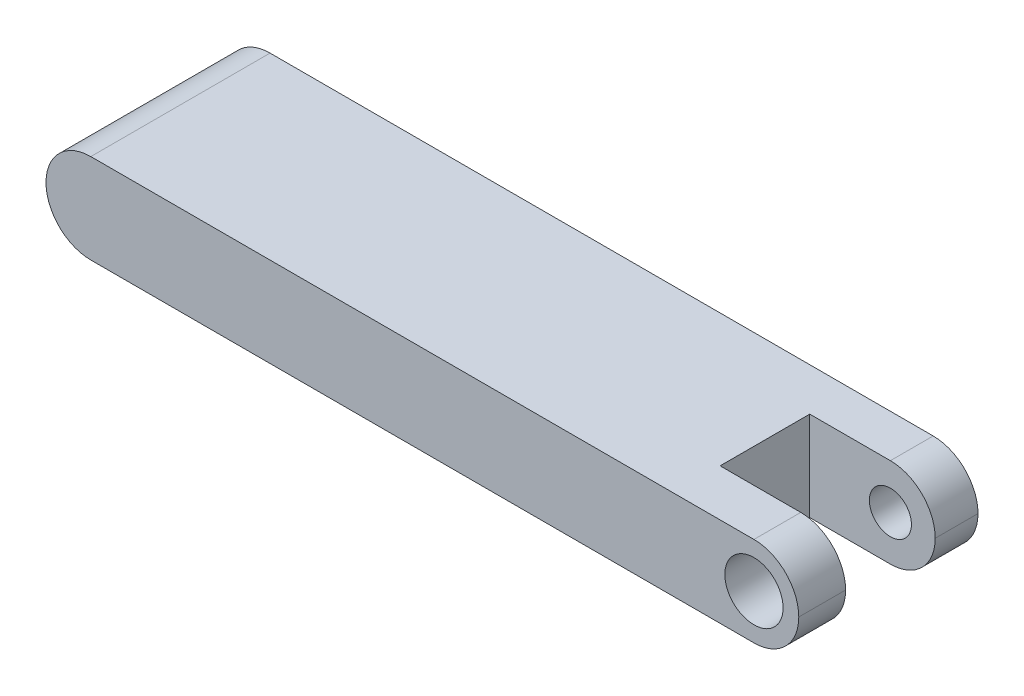
SolidWorks part; units mm, degrees
ref_plane "Front Plane" through (0, 0, 0) normal (0, 0, 1) x (1, 0, 0)
ref_plane "Top Plane" through (0, 0, 0) normal (0, 1, 0) x (1, 0, 0)
ref_plane "Right Plane" through (0, 0, 0) normal (1, 0, 0) x (0, 0, -1)
sketch "Sketch1" plane through (0, 0, 0) normal (0, 1, 0) x (1, 0, 0)
  line L0 (-8.89, 0) -> (12.446, 0)
  line L1 (12.446, 5.08) -> (-8.89, 5.08)
  line L2 (12.446, 0) -> (12.446, 5.08)
  line L3 (-8.89, 5.08) -> (-8.89, 0)
extrude "Boss-Extrude1" add sketch "Sketch1" along normal blind 2.54
fillet "Fillet1" radius 1.27 4 edges at (-8.89, 0, -2.54) (-8.89, 2.54, -2.54) (12.446, 0, -2.54) (12.446, 2.54, -2.54)
sketch "Sketch8" plane through (0, 2.54, 0) normal (0, 1, 0) x (1, 0, 0)
  line L0 (8.89, 3.8668) -> (8.89, 1.3268)
  line L1 (8.89, 3.8668) -> (12.446, 3.8668)
  line L2 (12.446, 5.08) -> (12.446, 0) construction
  line L3 (8.89, 1.3268) -> (12.446, 1.3268)
  line L4 (12.446, 1.3268) -> (12.446, 3.8668)
extrude "Cut-Extrude1" cut sketch "Sketch8" against normal blind 2.54
hole_wizard "#97 (0.0059) Diameter Hole1" positions "Sketch10" profile "Sketch9" hole size "#97" standard "ANSI Inch"
sketch "Sketch10" plane through (0, 0, 0) normal (0, 0, 1) x (1, 0, 0)
  point P0 (11.176, 1.27)
sketch "Sketch9" plane through (11.176, 1.27, 0) normal (1, 0, 0) x (0, -1, 0)
  line L0 (0, 0) -> (0, 2.02)
  line L1 (0, 2.02) -> (0.8255, 1.524)
  line L2 (0.8255, 1.524) -> (0.8255, 0)
  line L5 (0.8255, 0) -> (0, 0)
  line L10 (0, 2.02) -> (-0.8255, 1.524) construction
  line L11 (0, -6.35) -> (0, 107.95) construction
  dimension "Hole Dia." = 1.651
  dimension "Hole Depth" = 1.524
  dimension "Drill Angle" = 118
hole_wizard "#0-80 Tapped Hole1" positions "Sketch12" profile "Sketch11" tap size "#0-80" standard "ANSI Inch"
sketch "Sketch12" plane through (0, 0, -3.8668) normal (0, 0, 1) x (1, 0, 0)
  point P0 (11.176, 1.27)
sketch "Sketch11" plane through (11.176, 1.27, -3.8668) normal (1, 0, 0) x (0, -1, 0)
  line L0 (0, 0) -> (0, 4.4219)
  line L1 (0, 4.4219) -> (0.5956, 4.064)
  line L2 (0.5956, 4.064) -> (0.5956, 0)
  line L5 (0.5956, 0) -> (0, 0)
  line L10 (0, 4.4219) -> (-0.5956, 4.064) construction
  line L11 (0, -6.35) -> (0, 107.95) construction
  dimension "Tap Drill Dia." = 1.1913
  dimension "Tap Drill Depth" = 4.064
  dimension "Drill Angle" = 118
cosmetic thread "Hole Thread1" parameters "D1"=1.2132, "D2"=1.524
